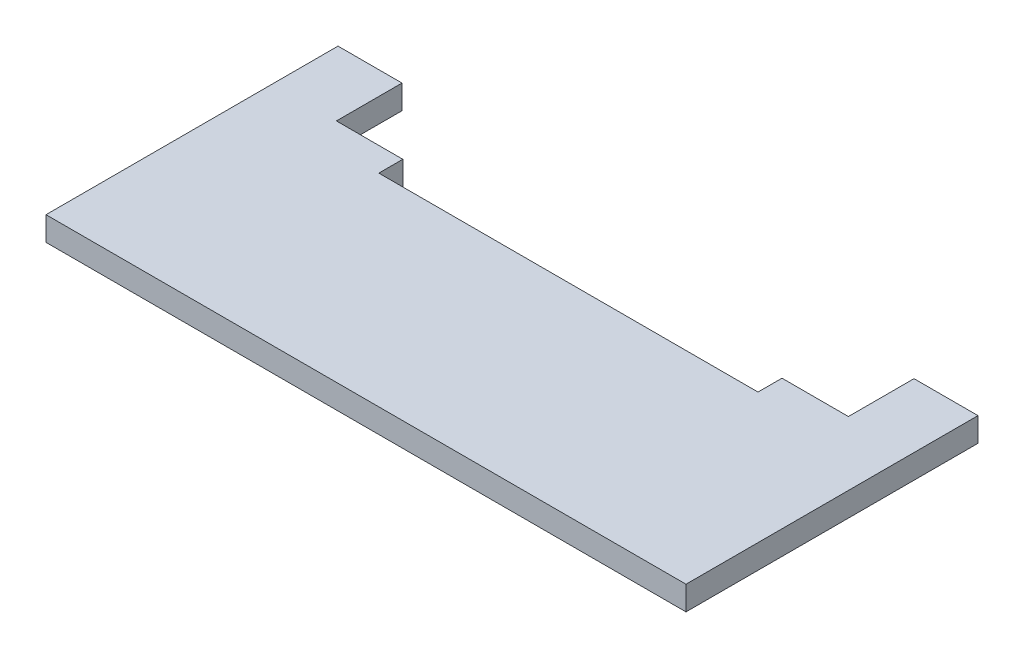
SolidWorks part; units mm, degrees
ref_plane "Front Plane" through (0, 0, 0) normal (0, 0, 1) x (1, 0, 0)
ref_plane "Top Plane" through (0, 0, 0) normal (0, 1, 0) x (1, 0, 0)
ref_plane "Right Plane" through (0, 0, 0) normal (1, 0, 0) x (0, 0, -1)
sketch "Sketch1" plane through (0, 0, 0) normal (0, 1, 0) x (1, 0, 0)
  line L0 (40, -36.5) -> (40, 0) construction
  line L1 (0, 0) -> (80, 0) construction
  line L2 (0, 0) -> (0, -36.5)
  line L3 (0, -36.5) -> (80, -36.5)
  line L4 (80, 0) -> (80, -36.5)
  line L5 (16.3, 0) -> (16.3, -3) construction
  line L6 (16.3, -3) -> (0, -3) construction
  line L7 (8, 0) -> (8, -8.2)
  line L8 (8, -8.2) -> (16.3, -8.2)
  line L9 (16.3, -8.2) -> (16.3, -11.2)
  line L10 (0, -11.2) -> (80, -11.2) construction
  line L11 (8, -11.2) -> (8, 0) construction
  line L12 (3, -3) -> (77, -3) construction
  line L13 (16.3, -8.2) -> (16.3, -11.2) construction
  line L15 (11, -8.2) -> (16.3, -8.2) construction
  line L16 (16.3, -11.2) -> (0, -11.2) construction
  line L17 (63.7, -8.2) -> (63.7, -11.2)
  line L18 (72, -8.2) -> (63.7, -8.2)
  line L19 (72, 0) -> (72, -8.2)
  line L20 (63.7, -11.2) -> (16.3, -11.2)
  line L21 (8, 0) -> (0, 0)
  line L22 (80, 0) -> (72, 0)
sketch "Sketch2" plane through (0, 0, 0) normal (0, 0, 1) x (1, 0, 0)
  line L1 (80, 0) -> (0, 0)
  line L2 (80, 0) -> (80, -3)
  line L3 (80, -3) -> (0, -3)
  line L4 (0, 0) -> (0, -3)
extrude "Boss-Extrude1" add sketch "Sketch1" against normal up to vertex (3 mm away) up to point (0, -3, 0)
